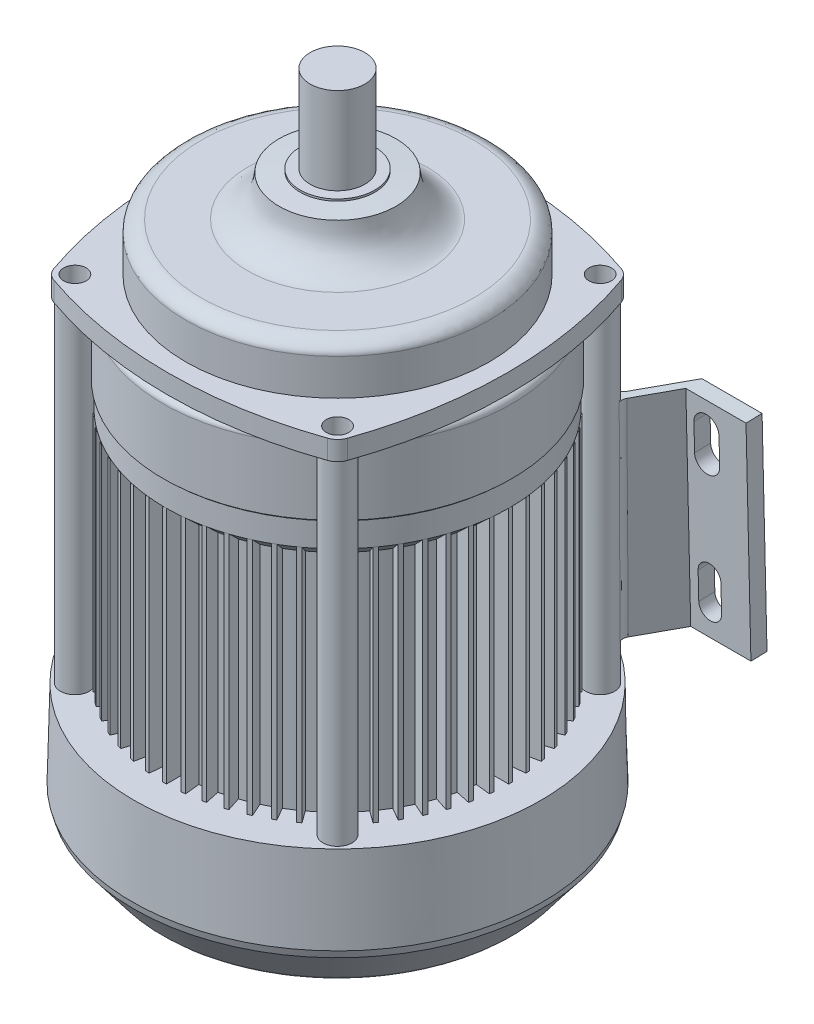
SolidWorks part; units mm, degrees
other "Motor Head"
other "Motor Base"
ref_plane "Front Plane" through (0, 0, 0) normal (0, 0, 1) x (1, 0, 0)
ref_plane "Top Plane" through (0, 0, 0) normal (0, 1, 0) x (1, 0, 0)
ref_plane "Right Plane" through (0, 0, 0) normal (1, 0, 0) x (0, 0, -1)
sketch "Sketch1" plane through (0, 0, 0) normal (0, 0, 1) x (1, 0, 0)
  line L0 (-69.3462, -139.209) -> (170.5518, -139.209) construction
  point P6 (0, 0)
sketch "Sketch3" plane through (0, 0, 0) normal (0, 0, 1) x (1, 0, 0)
  line L0 (-8.5, 0) -> (0, 0) construction
  line L1 (0, 8) -> (0, -197)
  line L2 (-8.5, 0) -> (-8.5, 8)
  line L3 (-8.5, 0) -> (-8.5, -10)
  line L4 (-8.5, -10) -> (-11.6, -10)
  line L5 (-11.6, -10) -> (-11.6, -10.6039)
  line L6 (-27.95, -23.6039) -> (-42.45, -23.6039)
  line L7 (-42.45, -23.6039) -> (-42.45, -27.2539) construction
  line L8 (-42.45, -27.2539) -> (-47.2, -27.2539) construction
  line L9 (-47.2, -27.2539) -> (-47.2, -44.5)
  line L10 (-45.45, -24.7539) -> (-45.45, -27.2539) construction
  line L11 (-11.6, -10.6039) -> (-18.2, -11.0655)
  line L12 (-22.2177, -20.8703) -> (-19.1856, -16.9994) construction
  line L13 (-20.1532, -29.2223) -> (-16.2468, 7.0914) construction
  line L14 (0, 8) -> (0, 17)
  line L15 (0, 17) -> (-8.5, 17)
  line L16 (-52.9, -44.5) -> (-47.2, -44.5)
  line L18 (0, 8) -> (0, 15.3127) construction
  line L19 (0, -197) -> (-2, -197)
  line L20 (-54.1917, -66.45) -> (-54.1917, -67.05) construction
  line L21 (-54.1917, -46.3) -> (-54.1917, -66.45)
  line L22 (-54.1917, -66.45) -> (-53.5483, -67.05)
  line L23 (-53.5483, -67.05) -> (-53.5483, -74.55)
  line L24 (-47.2, -44.5) -> (0, -44.5)
  line L25 (-52.9, -44.5) -> (0, -44.5) construction
  line L26 (-53.5483, -74.55) -> (-49.2588, -78.55)
  line L27 (-49.2588, -78.55) -> (-49.2588, -148.55)
  line L28 (-49.2588, -148.55) -> (-63.2588, -148.55)
  line L29 (-63.2588, -148.55) -> (-63.8951, -175.55)
  line L30 (-63.8951, -175.55) -> (-63.2588, -177.8444)
  line L31 (-63.2588, -177.8444) -> (-54.4331, -189.3444)
  line L32 (-8.5, 17) -> (-8.5, 8)
  line L33 (-63.2588, -148.55) -> (-63.2588, -175.55) construction
  arc A1 (-52.9, -44.5) -> (-54.1917, -46.3) centre (-52.2917, -46.3) ccw
  spline S0 degree 3 poles (-18.2, -11.0655) (-18.4832, -13.6984) (-18.7961, -16.5493) (-22.6179, -21.3727) (-26.2709, -23.6039) (-27.95, -23.6039) knots 0 0 0 0 0.435029 0.535029 1 1 1 1
  spline S2 degree 3 poles (-47.2, -27.2539) (-47.2, -26.1869) (-45.306, -24.4455) (-43.5167, -23.6039) (-42.45, -23.6039) knots 0 0 0 0 0.468038 1 1 1 1
  spline S3 degree 3 poles (-54.4331, -189.3444) (-51.4904, -193.1787) (-12.5784, -196.5978) (-6.2, -197) (-2, -197) knots 0 0 0 0 0.440369 1 1 1 1
  dimension "D13" = 6.6
  dimension "D14" = 52.5
  dimension "D21" = 1.9
  dimension "D23" = 1.8
  dimension "D37" = 14.5
  dimension "D38" = 5.5971
  dimension "D18" = 3.2012
  dimension "D19" = 3.2
  dimension "D22" = 12.6
  dimension "D39" = 8.827
  dimension "D2" = 3.65
  dimension "D3" = 4.75
  dimension "D4" = 2.5
  dimension "D5" = 3
  dimension "D6" = 10
  dimension "D7" = 3.1
  dimension "D8" = 0.6039
  dimension "D9" = 14.5
  dimension "D10" = 13
  dimension "D11" = 16.35
  dimension "D12" = 94
  dimension "D15" = 5.7
  dimension "D16" = 2
  dimension "D17" = 8
  dimension "D20" = 8.5
  dimension "D24" = 20.15
  dimension "D25" = 47
  dimension "D26" = 0.6
  dimension "D27" = 7.5
  dimension "D28" = 4
  dimension "D29" = 70
  dimension "D30" = 14
  dimension "D31" = 197
  dimension "D32" = 1.35
  dimension "D33" = 27
  dimension "D34" = 15.5
  dimension "D35" = 142.495
  dimension "D36" = 11.5
  dimension "D40" = 6.14
  dimension "D41" = 9
revolve "Revolve4" add sketch "Sketch3" angle 360 about L18 region at (-18.0879, -25.2086, 0) region at (-27.0884, -121.9509, 0)
sketch "Sketch5" plane through (0, -148.55, 0) normal (0, 1, 0) x (1, 0, 0)
  line L0 (0, 0) -> (0, -63.2588) construction
  line L1 (-0.625, -53.8549) -> (0.625, -53.8549)
  line L6 (-0.625, -53.8549) -> (-0.625, -49.2549)
  line L7 (0.625, -53.8549) -> (0.625, -49.2549)
  circle A0 centre (0, 0) radius 63.2588 construction
  circle A1 centre (0, 0) radius 49.2588 construction
  circle A2 centre (0, 0) radius 49.2588 construction
  arc A3 (-0.625, -49.2549) -> (0.625, -49.2549) centre (0, 0) ccw
  point P0 (0, 0)
  point P10 (0, -53.8549)
  dimension "D1" = 4.6
  dimension "D2" = 1.25
extrude "Boss-Extrude2" add sketch "Sketch5" along normal up to surface (74.2893 mm away) up to face at (0, -78.55, -49.2588)
pattern_circular "CirPattern1" count 60 over 360 about axis through (0, 8, 0) along (0, -1, 0) of "Boss-Extrude2"
ref_plane "Plane1" through (0, -38.5, 0) normal (0, 1, 0) x (1, 0, 0)
sketch "Sketch6" plane through (0, -38.5, 0) normal (0, 1, 0) x (1, 0, 0)
  line L0 (0, 0) -> (57.7588, 0) construction
  line L1 (0, 0) -> (40.8417, 40.8417) construction
  line L3 (-44.8417, -44.8417) -> (44.8417, -44.8417) construction
  line L4 (-44.8417, -44.8417) -> (-44.8417, 44.8417) construction
  line L5 (-44.8417, 44.8417) -> (44.8417, 44.8417) construction
  line L6 (44.8417, -44.8417) -> (44.8417, 44.8417) construction
  line L7 (-44.8417, -44.8417) -> (44.8417, 44.8417) construction
  line L8 (-44.8417, 44.8417) -> (44.8417, -44.8417) construction
  circle A0 centre (0, 0) radius 52.9 construction
  circle A1 centre (0, 0) radius 52.9 construction
  circle A2 centre (0, 0) radius 63.2588 construction
  circle A3 centre (0, 0) radius 63.2588 construction
  circle A4 centre (0, 0) radius 57.7588 construction
  circle A14 centre (-40.8417, 40.8417) radius 4.5
  circle A18 centre (40.8417, 40.8417) radius 3.5
  circle A19 centre (40.8417, -40.8417) radius 3.5
  circle A20 centre (-40.8417, -40.8417) radius 3.5
  circle A21 centre (-40.8417, 40.8417) radius 3.5
  arc A22 (44.8417, 44.8417) -> (44.8417, -44.8417) centre (-75.8927, 0) cw
  arc A23 (-44.8417, 44.8417) -> (44.8417, 44.8417) centre (0, -75.8927) cw
  arc A24 (-44.8417, 44.8417) -> (-44.8417, -44.8417) centre (75.8927, 0) ccw
  arc A25 (-44.8417, -44.8417) -> (44.8417, -44.8417) centre (0, 75.8927) ccw
  circle A26 centre (40.8417, 40.8417) radius 4.5
  circle A27 centre (40.8417, -40.8417) radius 4.5
  circle A28 centre (-40.8417, -40.8417) radius 4.5
  point P6 (0, 0)
  point P12 (52.9, 0)
  point P20 (0, 0)
  point P27 (0, -52.9)
  dimension "D3" = 7
  dimension "D1" = 5.5
  dimension "D2" = 45
  dimension "D5" = 4
  dimension "D6" = 4
  dimension "D7" = 1
  dimension "D8" = 1
  dimension "D4" = 4
extrude "Boss-Extrude5" add sketch "Sketch6" against normal up to surface (6 mm away) contours A24 A25 A22 A23 A28 A27 A26 A14 | A28 A20 | A27 A19 | A26 A18 | A14 A21 region at (-45.2144, -38.5, -40.8417) region at (0, -38.5, 0) region at (36.4689, -38.5, -40.8417) region at (36.4689, -38.5, 40.8417) region at (-45.2144, -38.5, 40.8417) up to face at (0, -44.5, -47.2)
extrude "Boss-Extrude6" add sketch "Sketch6<4>" against normal up to surface (110.05 mm away) contours A26 A18 | A14 A21 | A27 A19 | A28 A20 region at (-45.2144, -38.5, -40.8417) region at (36.4689, -38.5, -40.8417) region at (36.4689, -38.5, 40.8417) region at (-45.2144, -38.5, 40.8417) up to face at (0, -148.55, -63.2588)
sketch "Sketch6<4>" plane through (0, -38.5, 0) normal (0, 1, 0) x (1, 0, 0) same geometry as "Sketch6"
fillet "Fillet2" radius 5 4 edges at (44.8417, -41.5, 44.8417) (44.8417, -41.5, -44.8417) (-44.8417, -41.5, 44.8417) (-44.8417, -41.5, -44.8417)
ref_plane "Plane2" through (0, 1.4075, -59.7249) normal (0, 0.0236, -0.9997) x (-1, 0, 0)
sketch "Sketch7" plane through (0, 1.4075, -59.7249) normal (0, 0.0236, -0.9997) x (-1, 0, 0)
  line L0 (-58, -137.7) -> (-70.6, -137.7)
  line L1 (-70.6, -137.7) -> (-70.6, -72.8)
  line L2 (-70.6, -72.8) -> (-53.75, -72.8)
  line L3 (0, 0) -> (0, -214.7784) construction
  line L4 (-58.1192, -133.2) -> (-58.1192, -117.2) construction
  line L5 (-58.1192, -120.925) -> (-58.1192, -129.475) construction
  line L6 (-54.5692, -120.925) -> (-54.5692, -129.475)
  line L7 (-61.6692, -120.925) -> (-61.6692, -129.475)
  line L8 (-58.1192, -76.9) -> (-58.1192, -92.9) construction
  line L9 (-58.1192, -89.175) -> (-58.1192, -80.625) construction
  line L10 (-62.0192, -89.175) -> (-62.0192, -80.625)
  line L11 (-54.2192, -89.175) -> (-54.2192, -80.625)
  line L12 (-51.8792, -72.8) -> (-51.8792, -137.7)
  line L13 (-53.75, -72.8) -> (-51.8792, -72.8)
  line L14 (-58, -137.7) -> (-51.8792, -137.7)
  arc A0 (-54.5692, -120.925) -> (-61.6692, -120.925) centre (-58.1192, -120.925) ccw
  arc A1 (-61.6692, -129.475) -> (-54.5692, -129.475) centre (-58.1192, -129.475) ccw
  arc A2 (-62.0192, -89.175) -> (-54.2192, -89.175) centre (-58.1192, -89.175) ccw
  arc A3 (-54.2192, -80.625) -> (-62.0192, -80.625) centre (-58.1192, -80.625) ccw
  point P10 (-58.1192, -125.2)
  point P19 (-58.1192, -84.9)
  dimension "D10" = 3.55
  dimension "D13" = 3.9
  dimension "D1" = 58
  dimension "D2" = 137.7
  dimension "D3" = 12.6
  dimension "D4" = 72.8
  dimension "D5" = 53.75
  dimension "D6" = 16
  dimension "D7" = 4.5
  dimension "D8" = 58.1192
  dimension "D9" = 8.55
  dimension "D11" = 76.9
  dimension "D12" = 8.55
  dimension "D14" = 6.24
extrude "Boss-Extrude7" add sketch "Sketch7" against normal blind 5 separate body
sketch "Sketch9" plane through (0, -137.6618, -3.2442) normal (0, -0.9997, -0.0236) x (1, 0, 0)
  line L0 (51.8792, -54.7415) -> (43.2173, -39.9001)
  line L1 (51.8792, -59.7415) -> (40.8417, -40.8295)
  line L2 (51.8792, -59.7415) -> (51.8792, -54.7415)
  line L3 (40.8417, -40.8295) -> (43.2173, -39.9001)
  ellipse E0 centre (40.8417, -37.3305) end of major axis (44.3417, -37.3305) minor radius 3.499 construction
  ellipse E1 centre (40.8417, -37.3305) end of major axis (44.3417, -37.3305) minor radius 3.499 construction
  point P13 (40.8417, -37.3305)
extrude "Boss-Extrude8" add sketch "Sketch9" against normal up to surface (64.9 mm away) up to face at (61.2396, -71.4312, -58.9407)
mirror "Mirror2" about plane through (0, 0, 0) normal (1, 0, 0) of "Boss-Extrude8", "Boss-Extrude7"
extrude "Cut-Extrude1" cut sketch "Sketch6<5>" against normal up to surface (110.05 mm away) contours A18 | A21 region at (40.8417, -38.5, -40.8417) region at (-40.8417, -38.5, -40.8417) up to face at (-40.8417, -148.55, 36.3417)
sketch "Sketch6<5>" plane through (0, -38.5, 0) normal (0, 1, 0) x (1, 0, 0) same geometry as "Sketch6"
fillet "Fillet3" radius 2.5 4 edges at (-41.9484, -104.6306, -45.2034) (-44.1271, -103.8104, -43.9167) (41.9484, -104.6306, -45.2034) (44.1271, -103.8104, -43.9167)
ref_plane "Plane3" through (0, -148.55, 0) normal (0, 1, 0) x (1, 0, 0)
split "Split1" trim tools "Plane3" bodies to split 112 resulting bodies 113 114
ref_plane "Plane4" through (0, 0, -15) normal (0, 0, 1) x (1, 0, 0)
sketch "Sketch11" plane through (0, 0, -15) normal (0, 0, 1) x (1, 0, 0)
  line L0 (-58.8, -120.9) -> (-58.8, -138.4) construction
  dimension "D1" = 58.8
  dimension "D2" = 120.9
  dimension "D3" = 17.5
sketch "Sketch12" plane through (0, 0, 0) normal (1, 0, 0) x (0, 0, -1)
  line L0 (15, -120.9) -> (15, -138.4) construction
  line L4 (15, -134.65) -> (15, -124.65) construction
  line L5 (11.25, -134.65) -> (11.25, -124.65)
  line L6 (18.75, -134.65) -> (18.75, -124.65)
  arc A2 (11.25, -134.65) -> (18.75, -134.65) centre (15, -134.65) ccw
  arc A3 (18.75, -124.65) -> (11.25, -124.65) centre (15, -124.65) ccw
  point P0 (15, -120.9)
  point P5 (15, -129.65)
  point P10 (15, -120.9)
  dimension "D1" = 7.5
extrude "Boss-Extrude9" add sketch "Sketch12" against normal blind 62
fillet "Fillet4" radius 1 4 edges at (-62, -129.65, -18.75) (-62, -138.4, -15) (-62, -129.65, -11.25) (-62, -120.9, -15)
